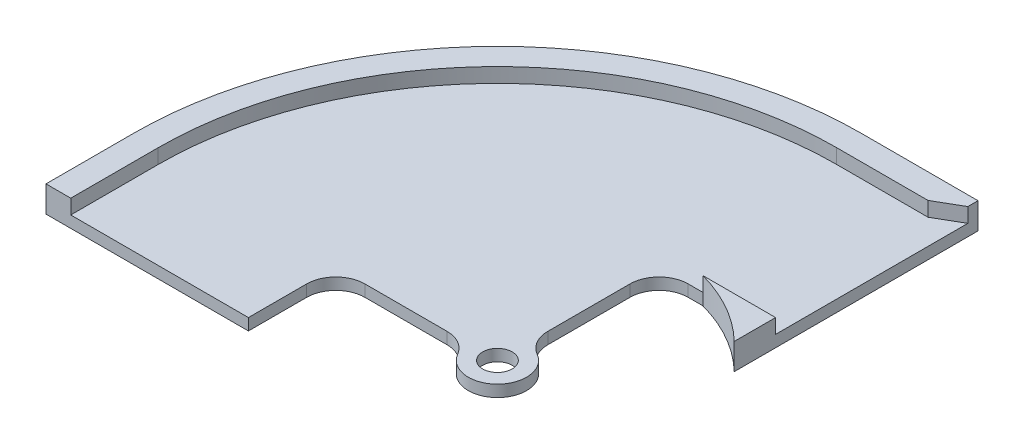
SolidWorks part; units mm, degrees
ref_plane "Front Plane" through (0, 0, 0) normal (0, 0, 1) x (1, 0, 0)
ref_plane "Top Plane" through (0, 0, 0) normal (0, 1, 0) x (1, 0, 0)
ref_plane "Right Plane" through (0, 0, 0) normal (1, 0, 0) x (0, 0, -1)
sketch "Sketch1" plane through (0, 0, 0) normal (0, 1, 0) x (1, 0, 0)
  line L1 (-62.5, 62.5) -> (62.5, 62.5)
  line L2 (-62.5, 62.5) -> (-62.5, -62.5)
  line L3 (-62.5, -62.5) -> (62.5, -62.5)
  line L4 (62.5, 62.5) -> (62.5, -62.5)
  line L5 (-62.5, 62.5) -> (62.5, -62.5) construction
  line L6 (-62.5, -62.5) -> (62.5, 62.5) construction
  circle A0 centre (62.5, -62.5) radius 55.5 construction
  point P0 (0, 0)
  dimension "D2" = 111
  dimension "D3" = 125
  dimension "D1" = 125
extrude "Boss-Extrude1" add sketch "Sketch1" along normal blind 4
sketch "Sketch7" plane through (0, 0, 0) normal (0, 1, 0) x (1, 0, 0)
  line L0 (62.5, 62.5) -> (62.5, -62.5) construction
  line L1 (62.5, -7) -> (102.5, -7)
  line L2 (62.5, -7) -> (62.5, 62.5)
  line L3 (62.5, 62.5) -> (102.5, 62.5)
  line L4 (102.5, -7) -> (102.5, 62.5)
  line L5 (-62.5, 62.5) -> (62.5, 62.5) construction
  circle A0 centre (62.5, -62.5) radius 55.5 construction
  dimension "D1" = 40
extrude "Boss-Extrude4" add sketch "Sketch7" along normal up to surface (4 mm away) up to face at (0, 4, 0)
sketch "Sketch8" plane through (0, 0, 0) normal (0, 1, 0) x (1, 0, 0)
  line L1 (-62.5, -62.5) -> (7, -62.5)
  line L2 (-62.5, -62.5) -> (-62.5, -92.5)
  line L3 (-62.5, -92.5) -> (7, -92.5)
  line L4 (7, -62.5) -> (7, -92.5)
  circle A0 centre (62.5, -62.5) radius 55.5 construction
  dimension "D1" = 30
extrude "Boss-Extrude5" add sketch "Sketch8" along normal up to surface (4 mm away) up to face at (34.1667, 4, 2.3333)
sketch "Sketch2" plane through (0, 4, 0) normal (0, 1, 0) x (1, 0, 0)
  line L0 (-62.5, -92.5) -> (-62.5, 62.5)
  line L1 (-62.5, 62.5) -> (102.5, 62.5)
  line L3 (62.5, -62.5) -> (62.5, -7) construction
  line L5 (7, -62.5) -> (62.5, -62.5) construction
  line L6 (62.5, 54) -> (102.5, 54)
  line L7 (102.5, -7) -> (102.5, 62.5) construction
  line L8 (102.5, 54) -> (102.5, 62.5)
  line L9 (-62.5, -92.5) -> (-54, -92.5)
  line L10 (-62.5, -92.5) -> (7, -92.5) construction
  line L11 (-54, -92.5) -> (-54, -62.5)
  arc A0 (-54, -62.5) -> (62.5, 54) centre (62.5, -62.5) cw
  circle A1 centre (62.5, -62.5) radius 55.5 construction
  dimension "D1" = 111
  dimension "D2" = 61
extrude "Boss-Extrude2" add sketch "Sketch2" along normal blind 5
sketch "Sketch3" plane through (0, 4, 0) normal (0, 1, 0) x (1, 0, 0)
  circle A0 centre (62.5, -62.5) radius 10
  dimension "D1" = 20
extrude "Boss-Extrude3" add sketch "Sketch3" against normal up to surface (4 mm away) up to face at (27.375, 0, 24.875)
sketch "Sketch4" plane through (0, 4, 0) normal (0, 1, 0) x (1, 0, 0)
  circle A0 centre (62.5, -62.5) radius 5.075
  dimension "D1" = 10.15
extrude "Cut-Extrude1" cut sketch "Sketch4" against normal up to surface (4 mm away) up to face at (31.5079, 0, 29.2857)
fillet "Fillet1" radius 125 1 edges at (-62.5, 4.5, -62.5)
chamfer "Chamfer1" distance 5 angle 60 1 edges at (102.5, 6.5, -54) first distance on face at (102.5, 4.3333, -36.5)
sketch "Sketch9" plane through (0, 0, 0) normal (0, 1, 0) x (1, 0, 0)
  line L0 (102.5, -7) -> (102.5, -21.1932)
  line L1 (102.5, -7) -> (77.5333, -7)
  line L2 (62.5, -7) -> (102.5, -7) construction
  arc A0 (77.5333, -7) -> (102.5, -21.1932) centre (62.5, -62.5) cw
  circle A1 centre (62.5, -62.5) radius 55.5 construction
  dimension "D1" = 2
extrude "Boss-Extrude6" add sketch "Sketch9" along normal up to surface (9 mm away) up to face at (15.6471, 9, -3.5574)
fillet "Fillet2" radius 10 4 edges at (62.5, 2, 7) (62.5, 2, 52.5) (52.5, 2, 62.5) (7, 2, 62.5)
